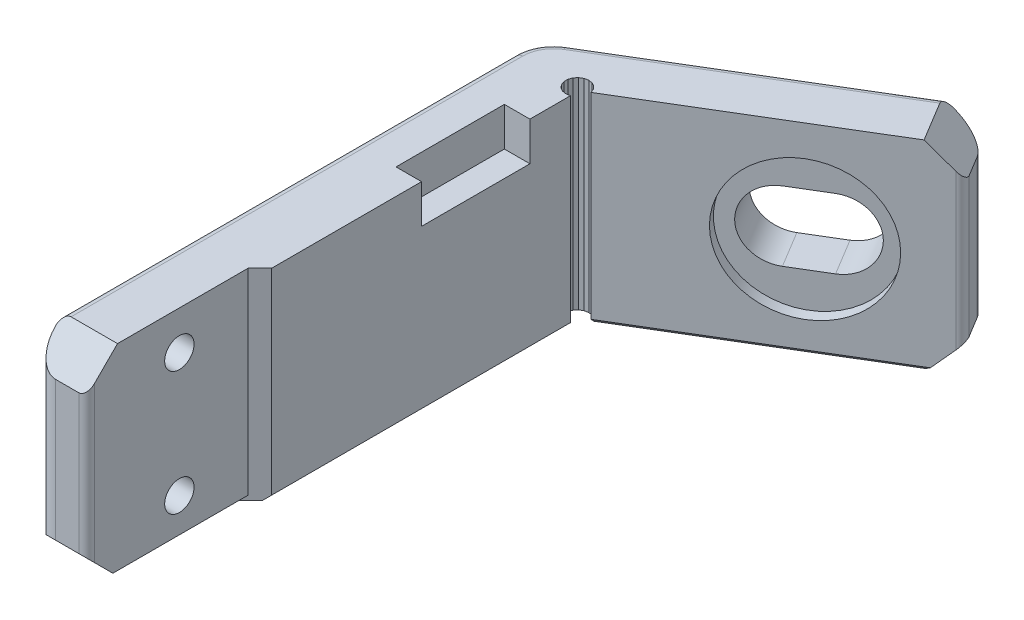
SolidWorks part; units mm, degrees
ref_plane "Front Plane" through (0, 0, 0) normal (0, 0, 1) x (1, 0, 0)
ref_plane "Top Plane" through (0, 0, 0) normal (0, 1, 0) x (1, 0, 0)
ref_plane "Right Plane" through (0, 0, 0) normal (1, 0, 0) x (0, 0, -1)
ref_plane "PY -20.700" through (0, -20.7, 0) normal (0, 1, 0) x (1, 0, 0)
sketch "leg and pad sketch" plane through (0, -20.7, 0) normal (0, 1, 0) x (1, 0, 0)
  line L0 (0.5513, 30.3327) -> (0.3673, 30.8194)
  line L1 (0.3673, 30.8194) -> (0.028, 31.2139)
  line L2 (0.028, 31.2139) -> (-0.4256, 31.4688)
  line L3 (-0.4256, 31.4688) -> (-0.939, 31.5534)
  line L4 (-0.939, 31.5534) -> (-1.4504, 31.4576)
  line L5 (-1.4504, 31.4576) -> (-1.8983, 31.1928)
  line L6 (-1.8983, 31.1928) -> (-2.2288, 30.7909)
  line L7 (-2.2288, 30.7909) -> (-2.4021, 30.3003)
  line L8 (-2.4021, 30.3003) -> (-2.3973, 29.78)
  line L9 (-2.3973, 29.78) -> (-2.2152, 29.2926)
  line L10 (-2.2152, 29.2926) -> (-1.8775, 28.8968)
  line L11 (-1.8775, 28.8968) -> (-1.4248, 28.6402)
  line L12 (-1.4248, 28.6402) -> (-0.9118, 28.5536)
  line L13 (-0.9118, 28.5536) -> (-0.4, 28.6475)
  line L14 (-0.4, 28.6475) -> (-0.4, -9.98)
  line L15 (-0.4, -9.98) -> (-1.92, -11.5)
  line L16 (-1.92, -11.5) -> (-1.92, -32.37)
  line L17 (-1.92, -32.37) -> (-8.92, -32.37)
  line L18 (-8.92, -32.37) -> (-8.92, 32.7926)
  line L19 (-8.92, 32.7926) -> (27.2048, 54.5947)
  line L20 (27.2048, 54.5947) -> (30.8218, 48.6015)
  line L21 (30.8218, 48.6015) -> (0.5513, 30.3327)
extrude "leg and pad" add sketch "leg and pad sketch" along normal mid plane 26
ref_plane "PX -1.350" through (-1.35, 0, 0) normal (1, 0, 0) x (0, 0, -1)
sketch "screw head relief sketch" plane through (-1.35, 0, 0) normal (1, 0, 0) x (0, 0, -1)
  line L0 (23.4, -12.7) -> (23.4, -6.7)
  line L1 (23.4, -6.7) -> (9.4, -6.7)
  line L2 (9.4, -6.7) -> (9.4, -12.7)
  line L3 (9.4, -12.7) -> (23.4, -12.7)
extrude "screw head relief" cut sketch "screw head relief sketch" against normal mid plane 4.7
sketch "insert flange relief sketch" plane through (0, -20.7, 0) normal (0, 1, 0) x (1, 0, 0)
  line L0 (18.3249, 39.8914) -> (17.0331, 42.0318)
  line L1 (17.0331, 42.0318) -> (9.3276, 37.3814)
  line L2 (9.3276, 37.3814) -> (10.6194, 35.241)
  line L3 (10.6194, 35.241) -> (18.3249, 39.8914)
revolve "insert flange relief" cut sketch "insert flange relief sketch" angle 360 about L0
sketch "M6 slot end 1 sketch" plane through (0, -20.7, 0) normal (0, 1, 0) x (1, 0, 0)
  line L0 (20.4653, 41.1832) -> (15.8149, 48.8886)
  line L1 (15.8149, 48.8886) -> (11.9621, 46.5634)
  line L2 (11.9621, 46.5634) -> (16.6125, 38.858)
  line L3 (16.6125, 38.858) -> (20.4653, 41.1832)
revolve "M6 slot end 1" cut sketch "M6 slot end 1 sketch" angle 360 about L0
sketch "M6 slot end 2 sketch" plane through (0, -20.7, 0) normal (0, 1, 0) x (1, 0, 0)
  line L0 (16.1845, 38.5996) -> (11.5341, 46.3051)
  line L1 (11.5341, 46.3051) -> (7.6813, 43.9799)
  line L2 (7.6813, 43.9799) -> (12.3317, 36.2744)
  line L3 (12.3317, 36.2744) -> (16.1845, 38.5996)
revolve "M6 slot end 2" cut sketch "M6 slot end 2 sketch" angle 360 about L0
sketch "M6 slot middle sketch" plane through (0, -20.7, 0) normal (0, 1, 0) x (1, 0, 0)
  line L0 (16.1845, 38.5996) -> (20.4653, 41.1832)
  line L1 (20.4653, 41.1832) -> (15.8149, 48.8886)
  line L2 (15.8149, 48.8886) -> (11.5341, 46.3051)
  line L3 (11.5341, 46.3051) -> (16.1845, 38.5996)
extrude "M6 slot middle" cut sketch "M6 slot middle sketch" against normal mid plane 9
ref_plane "PX -5.420" through (-5.42, 0, 0) normal (1, 0, 0) x (0, 0, -1)
sketch "screw holes sketch" plane through (-5.42, 0, 0) normal (1, 0, 0) x (0, 0, -1)
  circle A0 centre (-20.375, -28.7) radius 1.9
  circle A1 centre (-20.375, -12.7) radius 1.9
extrude "screw holes" cut sketch "screw holes sketch" against normal mid plane 9
chamfer "leg top corners" distance 4 angle 45 2 edges at (-5.42, -7.7, 32.37) (-5.42, -33.7, 32.37) tangent propagation no
chamfer "pad end corners" distance 4 angle 45 2 edges at (29.0133, -7.7, -51.5981) (29.0133, -33.7, -51.5981) tangent propagation no
fillet "outside of the bend" radius 5 1 edges at (-8.92, -20.7, -32.7926) tangent propagation no
fillet "leg top outer edge" radius 3 1 edges at (-8.92, -20.7, 32.37) tangent propagation no
fillet "pad end outer edge" radius 3 1 edges at (27.2048, -20.7, -54.5947) tangent propagation no
fillet "leg top inner edge" radius 1 1 edges at (-1.92, -20.7, 32.37) tangent propagation no
fillet "pad end inner edge" radius 1 1 edges at (30.8218, -20.7, -48.6015) tangent propagation no
chamfer "bed face chamfer" distance 0.6 angle 45 6 edges at (13.9742, -33.7, -38.4337) (8.6383, -33.7, -43.3894) (-1.92, -33.7, 19.935) (-0.4, -33.7, -9.3337) (-8.2742, -33.7, -32.4281) (-8.92, -33.7, -0.8001)
fillet "top face edge" radius 1 3 edges at (8.6383, -7.7, -43.3894) (-8.2742, -7.7, -32.4281) (-8.92, -7.7, -0.8001)
equation "\"diffL\" = 608.8mm"
equation "\"diffW\" = 329.4mm"
equation "\"diffT\" = 2.9mm"
equation "\"chanSlotW\" = 12.9mm"
equation "\"chanSlotDepth\" = 11.13mm"
equation "\"chanFloor\" = 1.57mm"
equation "\"chanLeg\" = 12.7mm"
equation "\"lightL\" = 605mm"
equation "\"lightW\" = 331mm"
equation "\"lightH\" = 92mm"
equation "\"lightSideFlat\" = 30mm"
equation "\"lightSlopeLen\" = 33.1mm"
equation "\"lightWingDepth\" = 47.9mm"
equation "\"lightWingFlat\" = 90.2mm"
equation "\"lightChanW\" = 99.6mm"
equation "\"lightChanStand\" = 44.1mm"
equation "\"insFlangeD\" = 12.3mm"
equation "\"insFromEnd\" = 20.7mm"
equation "\"insUpSlope\" = 20.8mm"
equation "\"gaugeH\" = 10mm"
equation "\"gaugeStepLen\" = 14mm"
equation "\"gaugeStepW0\" = 13.1mm"
equation "\"gaugeStepDW\" = 0.2mm"
equation "\"gaugeSteps\" = 5mm"
equation "\"gaugeHandleLen\" = 30mm"
equation "\"gaugeHandleW\" = 24mm"
equation "\"gaugeSlot0\" = 3mm"
equation "\"gaugeSlotD\" = 0.1mm"
equation "\"gaugeSlotDepth\" = 8mm"
equation "\"gap\" = 25.4mm"
equation "\"edgeL\" = 1mm"
equation "\"edgeW\" = 0.75mm"
equation "\"proud\" = 1.5mm"
equation "\"seatClr\" = 0.15mm"
equation "\"tongueClrZ\" = 0.1mm"
equation "\"tongueClrX\" = 0.25mm"
equation "\"tongueLen\" = 30mm"
equation "\"armSide\" = 45mm"
equation "\"armEnd\" = 20mm"
equation "\"cornerCham\" = 3mm"
equation "\"brkW\" = 26mm"
equation "\"brkT\" = 7mm"
equation "\"brkSeatClr\" = 0.2mm"
equation "\"brkScrewSpan\" = 16mm"
equation "\"pilotD\" = 2.7mm"
equation "\"pilotDepth\" = 10mm"
equation "\"screwClrD\" = 3.9mm"
equation "\"jogBelow\" = 4mm"
equation "\"padT\" = 7mm"
equation "\"padLen\" = 31mm"
equation "\"m6Clr\" = 7mm"
equation "\"m6Slot\" = 3mm"
equation "\"flangeRelD\" = 17mm"
equation "\"flangeRelDepth\" = 1.5mm"
equation "\"relLen\" = 7mm"
equation "\"relDepth\" = 4mm"
equation "\"relLand\" = 2mm"
equation "\"knockN\" = 100mm"
equation "\"petgcfE\" = 3000mm"
equation "\"mockExtent\" = 110mm"
equation "\"relZnear\" = 9.4mm"
equation "\"relZfar\" = 23.4mm"
equation "\"headD\" = 8mm"
equation "\"headH\" = 2.5mm"
equation "\"headFromEnd\" = 6.8mm"
equation "\"headBack\" = 16.4mm"
equation "\"sideClr\" = 0.4mm"
equation "\"cornerRelR\" = 1.5mm"
equation "\"cornerRelBack\" = 0.6mm"
equation "\"endHeadH\" = 2.8mm"
equation "\"footClr\" = 1.2mm"
equation "\"footEndClr\" = 3.5mm"
equation "\"footLift\" = 6mm"
equation "\"footBlockClr\" = 0.5mm"
equation "\"footBack\" = 50mm"
equation "\"footFwd\" = 10mm"
equation "\"footBraceEnd\" = 3mm"
equation "\"footLoadN\" = 25mm"
equation "\"spacerLen\" = 60mm"
equation "\"spacerShort\" = 0.5mm"
equation "\"spacerCham\" = 0.8mm"
equation "\"spacerPerSide\" = 3mm"
equation "\"spacerPerEnd\" = 1mm"
equation "\"toolR\" = 9mm"
equation "\"visR\" = 4mm"
equation "\"edgeR\" = 1mm"
equation "\"bendOutR\" = 5mm"
equation "\"insideR\" = 2.5mm"
equation "\"footCornerR\" = 10mm"
equation "\"footFrontR\" = 8mm"
equation "\"braceKinkR\" = 12mm"
equation "\"bedCham\" = 1mm"
equation "\"bedChamSmall\" = 0.6mm"
equation "\"soleTopR\" = 2mm"
equation "\"cornerR\" = 6mm"
equation "\"rimInR\" = 1mm"
equation "\"insFlangeH\" = 1mm"
equation "\"insHoleFinishD\" = 4.5mm"
equation "\"insLen\" = 6.4mm"
